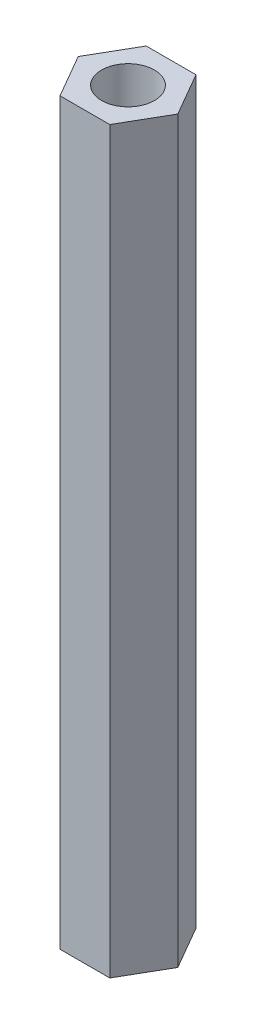
SolidWorks part; units mm, degrees
ref_plane "Front Plane" through (0, 0, 0) normal (0, 0, 1) x (1, 0, 0)
ref_plane "Top Plane" through (0, 0, 0) normal (0, 1, 0) x (1, 0, 0)
ref_plane "Right Plane" through (0, 0, 0) normal (1, 0, 0) x (0, 0, -1)
sketch "Sketch1" plane through (0, 0, 0) normal (0, 1, 0) x (1, 0, 0)
  line L1 (4.0415, 0) -> (2.0207, 3.5)
  line L2 (2.0207, 3.5) -> (-2.0207, 3.5)
  line L3 (-2.0207, 3.5) -> (-4.0415, 0)
  line L4 (-4.0415, 0) -> (-2.0207, -3.5)
  line L5 (-2.0207, -3.5) -> (2.0207, -3.5)
  line L6 (2.0207, -3.5) -> (4.0415, 0)
  circle A2 centre (0, 0) radius 3.5 construction
  circle A3 centre (0, 0) radius 2.15
  dimension "D1" = 7
  dimension "D2" = 4.3
extrude "Boss-Extrude1" add sketch "Sketch1" along normal blind 60
